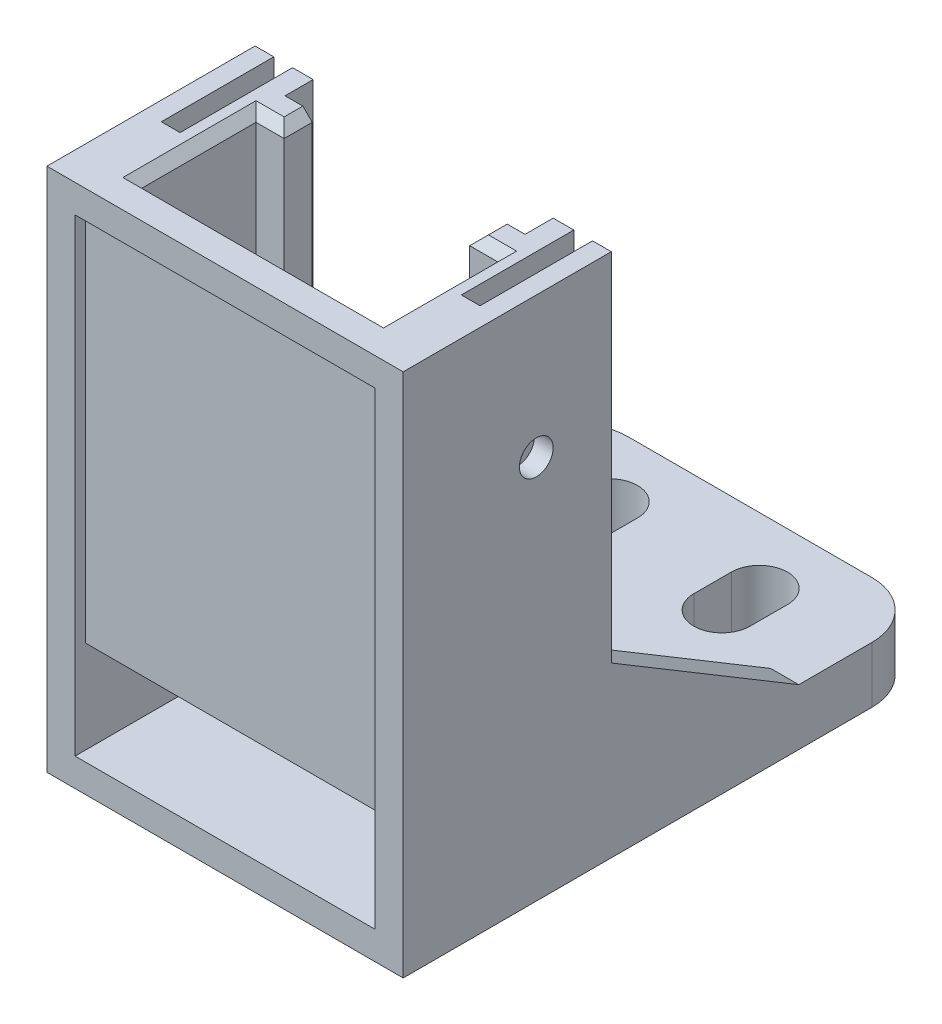
SolidWorks part; units mm, degrees
ref_plane "前视基准面" through (0, 0, 0) normal (0, 0, 1) x (1, 0, 0)
ref_plane "上视基准面" through (0, 0, 0) normal (0, 1, 0) x (1, 0, 0)
ref_plane "右视基准面" through (0, 0, 0) normal (1, 0, 0) x (0, 0, -1)
sketch "草图1" plane through (0, 0, 0) normal (0, 1, 0) x (1, 0, 0)
  line L0 (-57.4345, 0) -> (51.691, 0) construction
  line L1 (0, 59.2926) -> (0, -60.9819) construction
  line L2 (-9.5, 11.1) -> (-9.5, 0)
  line L3 (-9.5, 0) -> (9.5, 0)
  line L4 (9.5, 0) -> (9.5, 11.1)
  line L5 (9.5, 11.1) -> (4.95, 11.1)
  line L6 (-6.45, 8.1) -> (-6.45, 2)
  line L7 (-6.45, 2) -> (6.45, 2)
  line L8 (6.45, 2) -> (6.45, 8.1)
  line L9 (6.45, 8.1) -> (4.95, 8.1)
  line L10 (4.95, 8.1) -> (4.95, 11.1)
  line L11 (-6.45, 8.1) -> (-4.95, 8.1)
  line L12 (-4.95, 8.1) -> (-4.95, 11.1)
  line L13 (-4.95, 11.1) -> (-9.5, 11.1)
  dimension "D1" = 19
  dimension "D2" = 12.9
  dimension "D3" = 1.5
  dimension "D4" = 2
  dimension "D5" = 6.1
  dimension "D6" = 3
extrude "凸台-拉伸1" add sketch "草图1" along normal blind 25
sketch "草图2" plane through (0, 0, 0) normal (0, -1, 0) x (1, 0, 0)
  line L0 (9.5, 0) -> (-9.5, 0)
  line L1 (-9.5, 0) -> (-9.5, -28)
  line L2 (-9.5, -28) -> (9.5, -28)
  line L3 (9.5, -28) -> (9.5, 0)
  line L4 (0, -22.4608) -> (0, 12.6937) construction
  line L5 (-4, -22.5) -> (-4, -24.5) construction
  line L6 (-2.5, -22.5) -> (-2.5, -24.5)
  line L7 (-5.5, -22.5) -> (-5.5, -24.5)
  line L8 (4, -24.5) -> (4, -22.5) construction
  line L9 (2.5, -24.5) -> (2.5, -22.5)
  line L10 (5.5, -24.5) -> (5.5, -22.5)
  circle A0 centre (4, -24.5) radius 1.5 construction
  circle A1 centre (-4, -24.5) radius 1.5 construction
  arc A2 (-2.5, -22.5) -> (-5.5, -22.5) centre (-4, -22.5) ccw
  arc A3 (-5.5, -24.5) -> (-2.5, -24.5) centre (-4, -24.5) ccw
  arc A4 (2.5, -24.5) -> (5.5, -24.5) centre (4, -24.5) ccw
  arc A5 (5.5, -22.5) -> (2.5, -22.5) centre (4, -22.5) ccw
  point P14 (-4, -23.5)
  point P19 (4, -23.5)
  dimension "D3" = 3
  dimension "D1" = 28
  dimension "D2" = 8
  dimension "D4" = 3.5
  dimension "D5" = 2
extrude "凸台-拉伸2" add sketch "草图2" along normal blind 3
sketch "草图3" plane through (0, 25, 0) normal (0, 1, 0) x (1, 0, 0)
  line L0 (-8.5, 11.1) -> (-7.5, 11.1)
  line L1 (-4.95, 11.1) -> (-9.5, 11.1) construction
  line L2 (-7.5, 11.1) -> (-7.5, 5.1)
  line L3 (-7.5, 5.1) -> (-8.5, 5.1)
  line L4 (-8.5, 5.1) -> (-8.5, 11.1)
  line L5 (-9.5, 11.1) -> (-9.5, 0) construction
  line L7 (0, 11.5268) -> (0, -2.7437) construction
  line L8 (8.5, 5.1) -> (8.5, 11.1)
  line L9 (7.5, 5.1) -> (8.5, 5.1)
  line L10 (7.5, 11.1) -> (7.5, 5.1)
  line L11 (8.5, 11.1) -> (7.5, 11.1)
  dimension "D1" = 1
  dimension "D2" = 1
  dimension "D3" = 6
extrude "切除-拉伸1" cut sketch "草图3" against normal blind 15
sketch "草图4" plane through (-9.5, 0, 0) normal (-1, 0, 0) x (0, 0, 1)
  line L1 (-11.1, 25) -> (-11.1, 0) construction
  line L2 (-11.1, 25) -> (0, 25) construction
  circle A0 centre (-7.1, 17.5) radius 0.9
  dimension "D1" = 1.8
  dimension "D2" = 4
  dimension "D3" = 7.5
extrude "切除-拉伸2" cut sketch "草图4" against normal up to surface (19 mm away) up to face at (9.5, 7.3333, -13.0333)
fillet "圆角1" radius 3 2 edges at (9.5, -1.5, -28) (-9.5, -1.5, -28)
sketch "草图5" plane through (-9.5, 0, 0) normal (-1, 0, 0) x (0, 0, 1)
  line L0 (-11.1, 0) -> (-11.1, 6)
  line L1 (-11.1, 25) -> (-11.1, 0) construction
  line L2 (-11.1, 6) -> (-21.1, 0)
  line L3 (-11.1, 0) -> (-25, 0) construction
  line L4 (-21.1, 0) -> (-11.1, 0)
  dimension "D1" = 10
  dimension "D2" = 6
extrude "凸台-拉伸3" add sketch "草图5" against normal blind 1.5
mirror "镜向1" about plane through (0, 0, 0) normal (1, 0, 0) of "凸台-拉伸3"
sketch "草图6" plane through (0, 0, 0) normal (0, 1, 0) x (1, 0, 0)
  line L0 (-6.45, 2) -> (6.45, 2)
  line L1 (6.45, 2) -> (6.45, 8.1)
  line L2 (6.45, 8.1) -> (4.95, 8.1)
  line L3 (-6.45, 8.1) -> (-6.45, 2)
  line L4 (-4.95, 8.1) -> (-4.95, 11.1)
  line L5 (-4.95, 11.1) -> (4.95, 11.1)
  line L6 (4.95, 11.1) -> (4.95, 8.1)
  line L7 (-4.95, 8.1) -> (-6.45, 8.1)
extrude "凸台-拉伸4" add sketch "草图6" along normal blind 5
chamfer "倒角1" distance 0.5 angle 45 7 edges at (4.95, 25, -9.6) (-4.95, 25, -9.6) (-5.7, 25, -8.1) (5.7, 25, -8.1) (6.45, 25, -5.05) (0, 25, -2) (-6.45, 25, -5.05)
shell "抽壳1" thickness 1.5 removed face at (0, 11, 0) removed face at (-9.5, 17.5, -6.2) removed face at (9.5, 17.5, -6.2) removed face at (7.5, 17.5, -6.2) removed face at (-7.5, 17.5, -8)
sketch "草图7" plane through (0, -3, 0) normal (0, -1, 0) x (1, 0, 0)
  line L4 (8, -11.1) -> (-8, -11.1)
  line L5 (-1.7639, -26.5) -> (1.7639, -26.5)
  line L6 (6.2361, -26.5) -> (6.5, -26.5)
  line L7 (-8, 0) -> (-8, -26.5)
  line L8 (8, -26.5) -> (8, 0)
  line L9 (-8, -26.5) -> (8, -26.5)
  line L10 (-8, -11.1) -> (-8, -25)
  line L11 (8, -25) -> (8, -11.1)
  line L12 (-6.5, -26.5) -> (-6.2361, -26.5)
  line L13 (8, -9.6) -> (-8, -9.6) construction
  line L62 (4, -24.5) -> (4, -22.5) construction
  line L63 (1, -24.5) -> (1, -22.5)
  line L64 (7, -24.5) -> (7, -22.5)
  line L65 (-4, -24.5) -> (-4, -22.5) construction
  line L66 (-7, -24.5) -> (-7, -22.5)
  line L67 (-1, -24.5) -> (-1, -22.5)
  arc A0 (-8, -25) -> (-6.5, -26.5) centre (-6.5, -25) ccw
  arc A1 (8, -25) -> (6.5, -26.5) centre (6.5, -25) cw
  arc A2 (-1.7639, -26.5) -> (-1, -24.5) centre (-4, -24.5) ccw
  arc A3 (6.2361, -26.5) -> (7, -24.5) centre (4, -24.5) ccw
  arc A49 (1, -24.5) -> (1.7639, -26.5) centre (4, -24.5) ccw
  arc A50 (7, -22.5) -> (1, -22.5) centre (4, -22.5) ccw
  arc A51 (-7, -24.5) -> (-6.2361, -26.5) centre (-4, -24.5) ccw
  arc A52 (-1, -22.5) -> (-7, -22.5) centre (-4, -22.5) ccw
  point P2 (4, -23.5)
  point P8 (-4, -23.5)
  dimension "D1" = 3
  dimension "D3" = 1.5
  dimension "D4" = 1.5
  dimension "D2" = 1.5
extrude "切除-拉伸3" cut sketch "草图7" against normal blind 1.5
sketch "草图8" plane through (0, 0, -11.1) normal (0, 0, -1) x (-1, 0, 0)
  line L0 (6.4, 25) -> (-6.4, 25)
  line L1 (5.45, 25) -> (7.5, 25) construction
  line L2 (-7.5, 25) -> (-5.45, 25) construction
  line L3 (-6.4, 25) -> (-6.4, 5)
  line L4 (-6.4, 5) -> (6.4, 5)
  line L5 (6.4, 5) -> (6.4, 25)
  line L6 (7.5, 10) -> (7.5, 25) construction
  line L7 (-7.5, 10) -> (-7.5, 25) construction
  dimension "D1" = 1.1
  dimension "D2" = 1.1
extrude "切除-拉伸4" cut sketch "草图8" against normal blind 1.5
